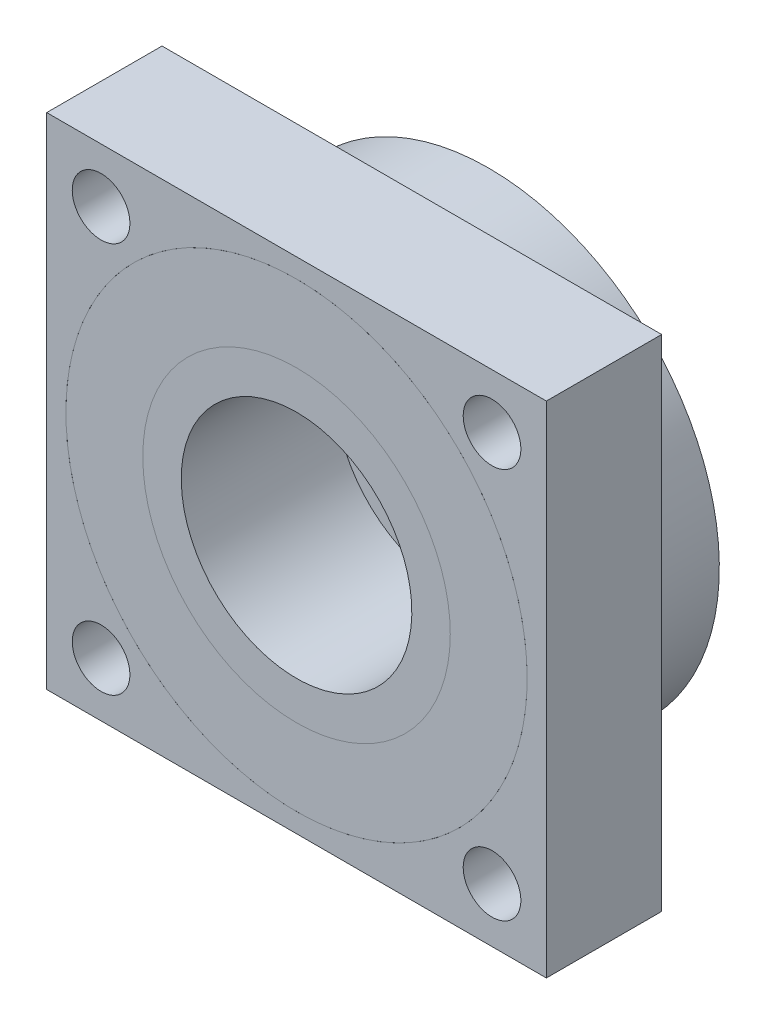
SolidWorks part; units mm, degrees
material "6061 Alloy"
ref_plane "Front Plane" through (0, 0, 0) normal (0, 0, 1) x (1, 0, 0)
ref_plane "Top Plane" through (0, 0, 0) normal (0, 1, 0) x (1, 0, 0)
ref_plane "Right Plane" through (0, 0, 0) normal (1, 0, 0) x (0, 0, -1)
sketch "Sketch1" plane through (0, 0, 0) normal (1, 0, 0) x (0, 0, -1)
  line L0 (12.7, 0) -> (0, 0) construction
  line L1 (12.7, 0) -> (12.7, 10.16)
  line L2 (12.7, 10.16) -> (0, 10.16)
  line L3 (12.7, 0) -> (0, 0)
  line L4 (0, 10.16) -> (0, 0)
  line L5 (0, 7.62) -> (12.7, 7.62)
  line L6 (0, 10.16) -> (0, 15.24)
  line L7 (0, 15.24) -> (12.7, 15.24)
  line L8 (12.7, 15.24) -> (12.7, 10.16)
  dimension "D1" = 10.16
  dimension "D2" = 12.7
  dimension "D3" = 7.62
  dimension "D4" = 5.08
revolve "Revolve2" add sketch "Sketch1" angle 360 about L0 region at (0, 12.7, -6.35)
revolve "Revolve3" add sketch "Sketch1<4>" angle 360 about L0 region at (0, 8.89, -6.35)
sketch "Sketch1<4>" plane through (0, 0, 0) normal (1, 0, 0) x (0, 0, -1) same geometry as "Sketch1"
sketch "Sketch2" plane through (0, 0, 0) normal (0, 0, 1) x (1, 0, 0)
  circle A0 centre (0, 12.7) radius 1.905
  circle A1 centre (12.7, 0) radius 1.905
  circle A2 centre (0, -12.7) radius 1.905
  circle A3 centre (-12.7, 0) radius 1.905
  point P12 (0, 0)
  dimension "D1" = 3.81
  dimension "D2" = 12.7
  dimension "D3" = 4
sketch "Sketch3" plane through (0, 0, 0) normal (0, 0, 1) x (1, 0, 0)
  line L1 (-16.51, 16.51) -> (16.51, 16.51)
  line L2 (-16.51, 16.51) -> (-16.51, -16.51)
  line L3 (-16.51, -16.51) -> (16.51, -16.51)
  line L4 (16.51, 16.51) -> (16.51, -16.51)
  line L5 (-16.51, 16.51) -> (16.51, -16.51) construction
  line L6 (-16.51, -16.51) -> (16.51, 16.51) construction
  circle A0 centre (0, 0) radius 15.24
  circle A1 centre (0, 0) radius 15.24 construction
  point P0 (0, 0)
  dimension "D1" = 33.02
  dimension "D2" = 33.02
extrude "Boss-Extrude1" add sketch "Sketch3" against normal blind 7.62 separate body
sketch "Sketch4" plane through (0, 0, -7.62) normal (0, 0, -1) x (-1, 0, 0)
  line L0 (-16.51, 16.51) -> (0, 0) construction
  circle A0 centre (-12.9179, 12.9179) radius 1.905
  circle A1 centre (12.9179, 12.9179) radius 1.905
  circle A2 centre (12.9179, -12.9179) radius 1.905
  circle A3 centre (-12.9179, -12.9179) radius 1.905
  point P15 (0, 0)
  dimension "D1" = 3.81
  dimension "D2" = 5.08
  dimension "D3" = 4
extrude "Cut-Extrude2" cut sketch "Sketch4" against normal through all
sketch "Sketch5" plane through (0, 0, 0) normal (0, 0, 1) x (1, 0, 0)
  circle A1 centre (0, 0) radius 10.16
  circle A2 centre (0, 0) radius 10.16
  dimension "D1" = 0
extrude "Boss-Extrude3" add sketch "Sketch5" along normal blind 2.54 from surface separate body starting at face at (0, 10.16, -12.7)
combine bodies "Combine1" operation type add bodies to combine 103 108
